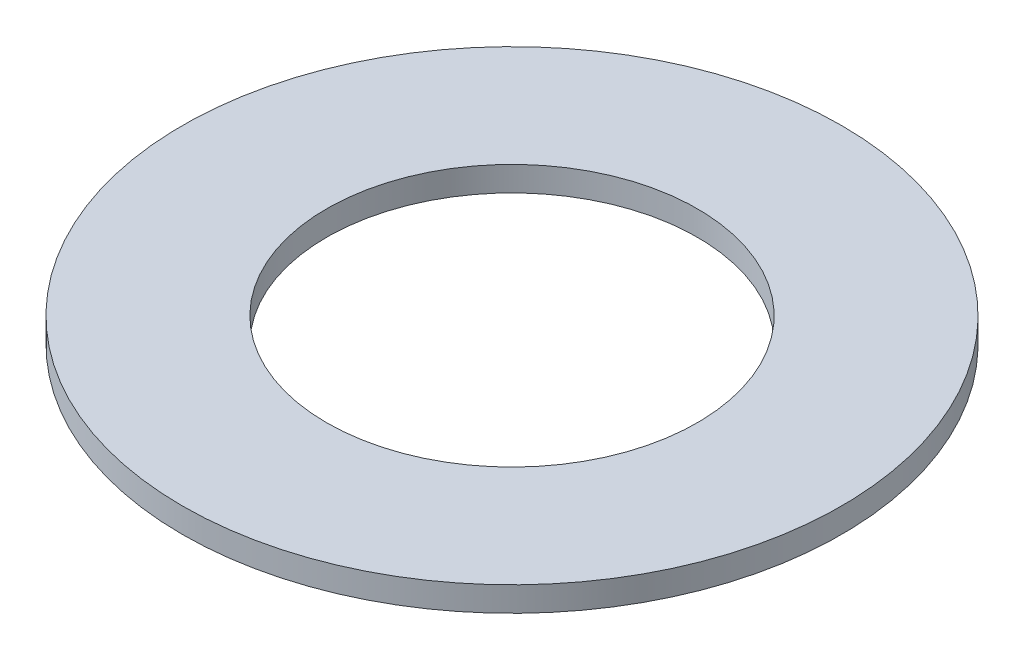
SolidWorks part; units mm, degrees
ref_plane "Front Plane" through (0, 0, 0) normal (0, 0, 1) x (1, 0, 0)
ref_plane "Top Plane" through (0, 0, 0) normal (0, 1, 0) x (1, 0, 0)
ref_plane "Right Plane" through (0, 0, 0) normal (1, 0, 0) x (0, 0, -1)
sketch "Sketch1" plane through (0, 0, 0) normal (0, 1, 0) x (1, 0, 0)
  circle A0 centre (0, 0) radius 80
  dimension "FLANGE_OD" = 160
extrude "Boss-Extrude1" add sketch "Sketch1" along normal blind 6
sketch "Sketch2" plane through (0, 0, 0) normal (0, 1, 0) x (1, 0, 0)
  circle A0 centre (0, 0) radius 45
  dimension "BORE_D" = 90
extrude "Cut-Extrude1" cut sketch "Sketch2" along normal through all
sketch "Sketch3" plane through (0, 6, 0) normal (0, 1, 0) x (1, 0, 0)
  circle A0 centre (0, 0) radius 25.9755 construction
  circle A1 centre (-25.9755, 0) radius 4.621
  dimension "BOLT_D" = 9.242
  dimension "BOLT_PCD" = 51.951
extrude "Cut-Extrude2" cut sketch "Sketch3" against normal blind 4.4863 rebuild error yes
pattern_circular "CirPattern1" count 5 over 360 rebuild error yes
